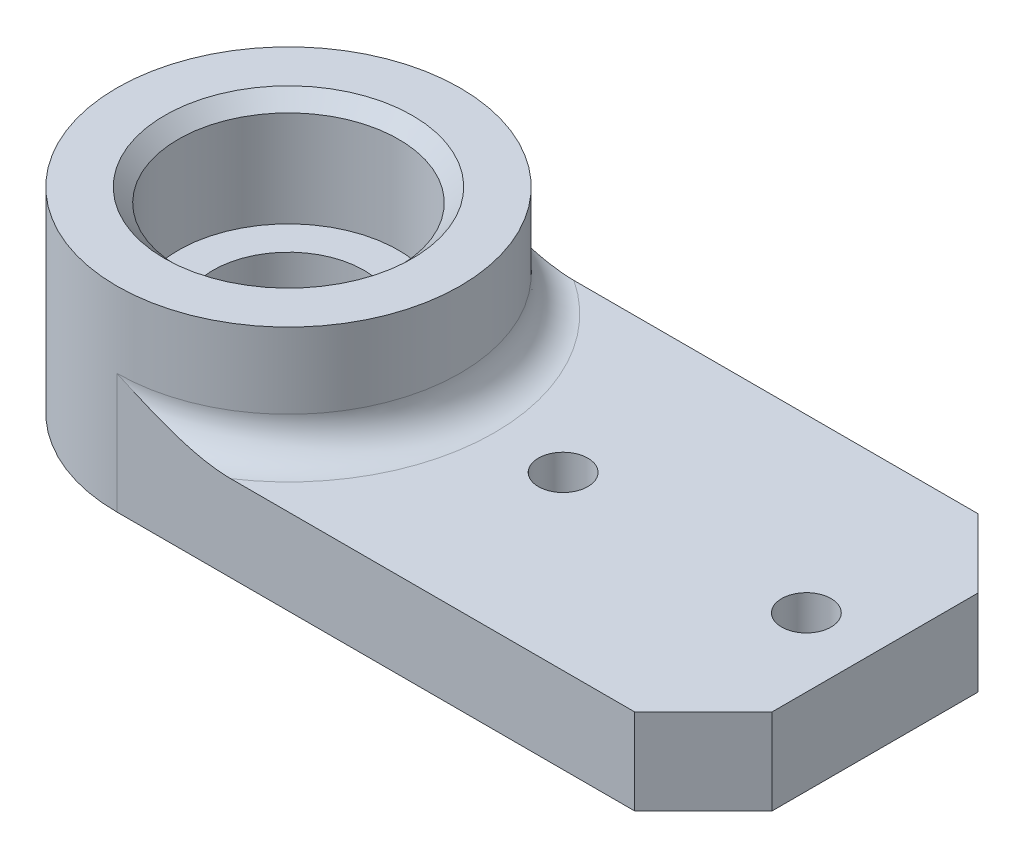
SolidWorks part; units mm, degrees
material "PLA"
ref_plane "Front Plane" through (0, 0, 0) normal (0, 0, 1) x (1, 0, 0)
ref_plane "Top Plane" through (0, 0, 0) normal (0, 1, 0) x (1, 0, 0)
ref_plane "Right Plane" through (0, 0, 0) normal (1, 0, 0) x (0, 0, -1)
sketch "Sketch1" plane through (0, 0, 0) normal (0, 1, 0) x (1, 0, 0)
  circle A0 centre (0, 0) radius 4.0767
  circle A1 centre (0, 0) radius 6.35
  dimension "D1" = 8.1534
  dimension "D2" = 12.7
extrude "Bearing-Housing" add sketch "Sketch1" along normal blind 4.064
sketch "Sketch2" plane through (0, 0, 0) normal (0, -1, 0) x (1, 0, 0)
  circle A0 centre (0, 0) radius 6.35 construction
  circle A1 centre (0, 0) radius 6.35
  circle A2 centre (0, 0) radius 2.794
  dimension "D1" = 5.588
extrude "Cap" add sketch "Sketch2" along normal blind 3.175
sketch "Sketch3" plane through (0, -3.175, 0) normal (0, 1, 0) x (1, 0, 0)
  line L0 (0, 6.35) -> (21.6992, 6.35)
  line L1 (21.6992, 6.35) -> (21.6992, -6.35)
  line L2 (21.6992, -6.35) -> (0, -6.35)
  line L3 (0, 0) -> (21.6992, 0) construction
  circle A0 centre (0, 0) radius 6.35 construction
  arc A2 (0, -6.35) -> (0, 6.35) centre (0, 0) ccw
  circle A3 centre (19.1592, 0) radius 0.9144
  circle A4 centre (10.16, 0) radius 0.9144
  dimension "D5" = 1.8288
  dimension "D1" = 10.16
  dimension "D2" = 2.54
  dimension "D3" = 8.9992
extrude "Extender" add sketch "Sketch3" along normal blind 3.175
fillet "Fillet1" radius 1.27 1 edges at (6.35, 0, 0)
chamfer "Chamfer1" distance 0.508 angle 45 1 edges at (0, 4.064, 4.0767)
chamfer "Chamfer2" distance 2.54 angle 45 2 edges at (21.6992, -1.5875, 6.35) (21.6992, -1.5875, -6.35)
